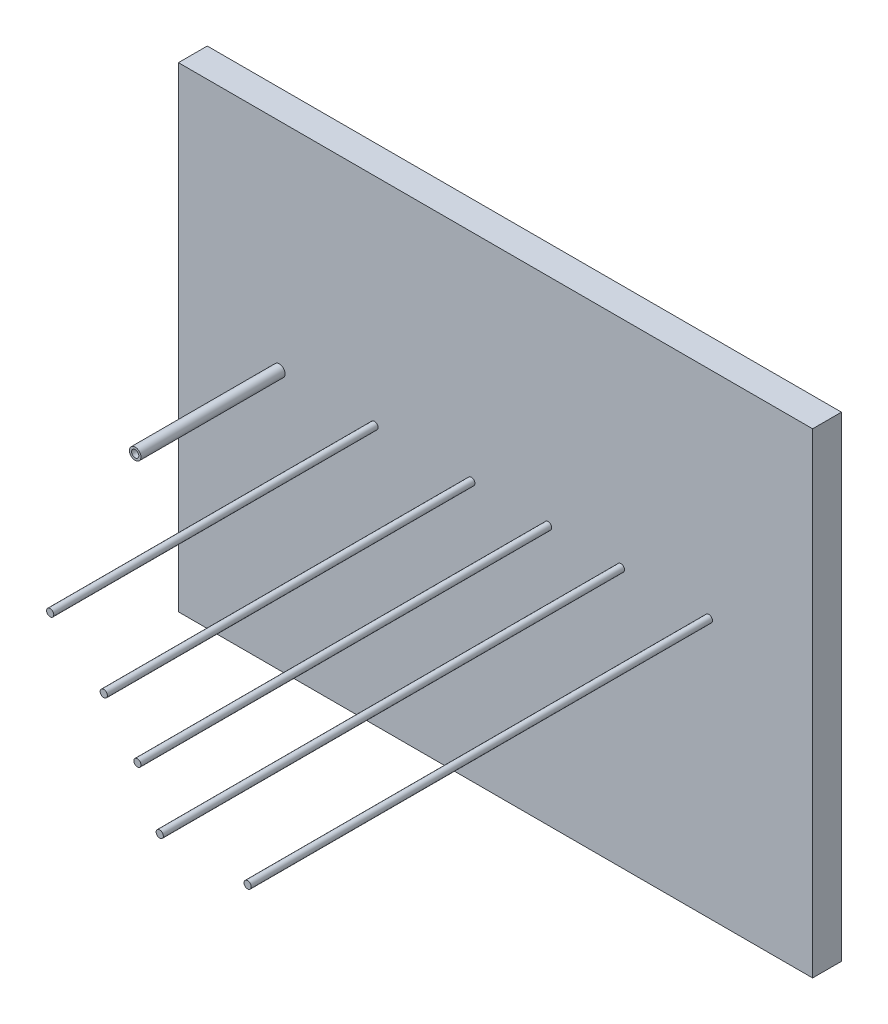
SolidWorks part; units mm, degrees
ref_plane "Alzado" through (0, 0, 0) normal (0, 0, 1) x (1, 0, 0)
ref_plane "Planta" through (0, 0, 0) normal (0, 1, 0) x (1, 0, 0)
ref_plane "Vista lateral" through (0, 0, 0) normal (1, 0, 0) x (0, 0, -1)
sketch "Croquis1" plane through (0, 0, 0) normal (0, 0, 1) x (1, 0, 0)
  line L1 (0, 0) -> (440, 0)
  line L2 (0, 0) -> (0, 330)
  line L3 (0, 330) -> (440, 330)
  line L4 (440, 0) -> (440, 330)
  line L5 (0, 0) -> (440, 330) construction
  line L6 (0, 330) -> (440, 0) construction
  point P4 (220, 165)
  dimension "D1" = 330
  dimension "D2" = 440
extrude "Saliente-Extruir1" add sketch "Croquis1" along normal blind 20
sketch "Croquis3" plane through (0, 0, 20) normal (0, 0, 1) x (1, 0, 0)
  line L0 (0, 0) -> (440, 0) construction
  line L1 (0, 330) -> (0, 0) construction
  circle A0 centre (70, 180) radius 4
  circle A1 centre (136, 180) radius 2.5
  circle A2 centre (203.2, 180) radius 2.5
  circle A4 centre (256.5, 180) radius 2.5
  circle A5 centre (307, 180) radius 2.5
  circle A6 centre (368, 180) radius 2.5
  point P14 (0, 0)
  point P15 (0, 0)
  point P16 (0, 0)
  point P19 (0, 0)
  point P20 (0, 0)
  point P21 (0, 0)
  point P22 (0, 0)
  dimension "D1" = 8
  dimension "D2" = 5
  dimension "D3" = 5
  dimension "D4" = 5
  dimension "D10" = 5
  dimension "D12" = 5
  dimension "D5" = 66
  dimension "D6" = 67.2
  dimension "D8" = 180
  dimension "D7" = 53.3
  dimension "D9" = 70
  dimension "D11" = 50.5
  dimension "D13" = 61
extrude "Saliente-Extruir2" add sketch "Croquis3" along normal blind 100 contours A0 region at (70, 180, 20)
sketch "Croquis5" plane through (0, 0, 120) normal (0, 0, 1) x (1, 0, 0)
  circle A0 centre (70, 180) radius 2.5
  dimension "D1" = 5
extrude "Cortar-Extruir2" cut sketch "Croquis5" against normal blind 100
extrude "Saliente-Extruir3" add sketch "Croquis3<3>" along normal blind 225 contours A1
sketch "Croquis3<3>" plane through (0, 0, 20) normal (0, 0, 1) x (1, 0, 0) same geometry as "Croquis3"
extrude "Saliente-Extruir4" add sketch "Croquis3<4>" along normal blind 255 contours A2
sketch "Croquis3<4>" plane through (0, 0, 20) normal (0, 0, 1) x (1, 0, 0) same geometry as "Croquis3"
extrude "Saliente-Extruir5" add sketch "Croquis3<5>" along normal blind 255 contours A2
sketch "Croquis3<5>" plane through (0, 0, 20) normal (0, 0, 1) x (1, 0, 0) same geometry as "Croquis3"
extrude "Saliente-Extruir6" add sketch "Croquis3<6>" along normal blind 285 contours A4
sketch "Croquis3<6>" plane through (0, 0, 20) normal (0, 0, 1) x (1, 0, 0) same geometry as "Croquis3"
extrude "Saliente-Extruir7" add sketch "Croquis3<7>" along normal blind 320 contours A5 | A6
sketch "Croquis3<7>" plane through (0, 0, 20) normal (0, 0, 1) x (1, 0, 0) same geometry as "Croquis3"
equation "\"DistEjes1\"= 66"
equation "\"D5@Croquis3\"=\"DistEjes1\""
equation "\"DistEjes2\"= 67.2"
equation "\"D6@Croquis3\"=\"DistEjes2\""
equation "\"DistEjes3\"= 53.3"
equation "\"DistVertEjes\"=186.529"
equation "\"D7@Croquis3\"=\"DistEjes3\""
equation "\"DistHorEjes\"=63.0918"
equation "\"DistEjes4\"=50.5"
equation "\"D11@Croquis3\"=\"DistEjes4\""
equation "\"DistEjes5\" = 61"
equation "\"D13@Croquis3\"=\"DistEjes5\""
equation "\"LargoBase\"=330"
equation "\"D1@Croquis1\"=\"LargoBase\""
equation "\"AnchoBase\" = 440"
equation "\"D2@Croquis1\"=\"AnchoBase\""
